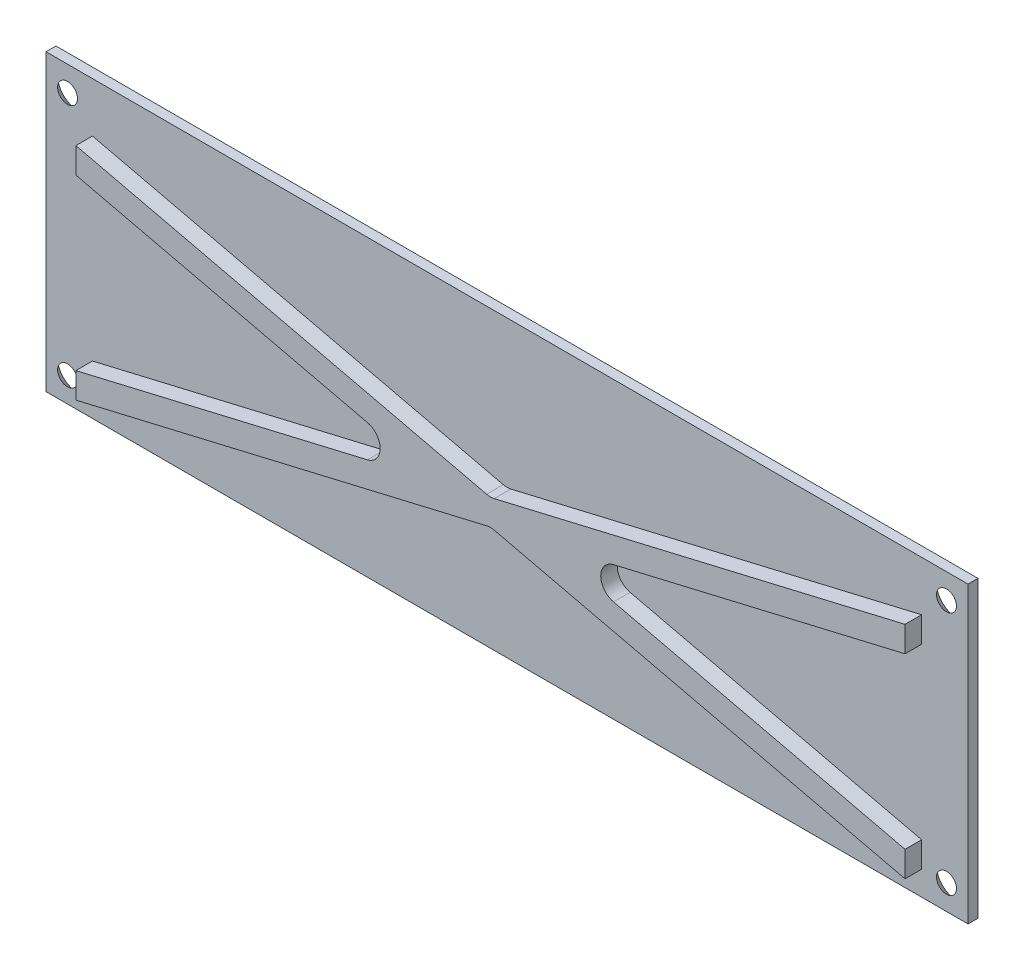
SolidWorks part; units mm, degrees
ref_plane "Front Plane" through (0, 0, 0) normal (0, 0, 1) x (1, 0, 0)
ref_plane "Top Plane" through (0, 0, 0) normal (0, 1, 0) x (1, 0, 0)
ref_plane "Right Plane" through (0, 0, 0) normal (1, 0, 0) x (0, 0, -1)
sketch "Sketch1" plane through (0, 0, 0) normal (0, 0, 1) x (1, 0, 0)
  line L1 (-56, -17.75) -> (56, -17.75)
  line L2 (-56, -17.75) -> (-56, 17.75)
  line L3 (-56, 17.75) -> (56, 17.75)
  line L4 (56, -17.75) -> (56, 17.75)
  line L5 (-56, -17.75) -> (56, 17.75) construction
  line L6 (-56, 17.75) -> (56, -17.75) construction
  point P0 (0, 0)
  dimension "D1" = 112
  dimension "D2" = 35.5
extrude "Boss-Extrude1" add sketch "Sketch1" along normal blind 1.2
sketch "Sketch2" plane through (0, 0, 1.2) normal (0, 0, 1) x (1, 0, 0)
  line L0 (0, -17.75) -> (0, 17.75) construction
  line L1 (-56, 17.75) -> (-50, 17.75)
  line L2 (-56, 17.75) -> (-56, 11.75)
  line L3 (-56, 11.75) -> (-50, 11.75)
  line L4 (-50, 17.75) -> (-50, 11.75)
  line L5 (-56, -17.75) -> (56, -17.75) construction
  line L6 (56, 17.75) -> (-56, 17.75) construction
  line L7 (-56, 0) -> (56, 0) construction
  line L8 (-56, 17.75) -> (-56, -17.75) construction
  line L9 (56, -17.75) -> (56, 17.75) construction
  line L10 (-50, -17.75) -> (-50, -11.75)
  line L11 (-56, -11.75) -> (-50, -11.75)
  line L12 (-56, -17.75) -> (-56, -11.75)
  line L13 (-56, -17.75) -> (-50, -17.75)
  line L14 (56, -17.75) -> (50, -17.75)
  line L15 (56, -17.75) -> (56, -11.75)
  line L16 (56, -11.75) -> (50, -11.75)
  line L17 (50, -17.75) -> (50, -11.75)
  line L18 (50, 17.75) -> (50, 11.75)
  line L19 (56, 11.75) -> (50, 11.75)
  line L20 (56, 17.75) -> (56, 11.75)
  line L21 (56, 17.75) -> (50, 17.75)
  dimension "D1" = 6
extrude "Boss-Extrude2" add sketch "Sketch2" along normal blind 2
sketch "Sketch3" plane through (0, 0, 3.2) normal (0, 0, 1) x (1, 0, 0)
  line L0 (-56, 0) -> (56, 0) construction
  line L1 (-56, 11.75) -> (-56, -11.75) construction
  line L2 (56, -11.75) -> (56, 11.75) construction
  line L3 (0, 17.75) -> (0, -17.75) construction
  line L4 (50, 17.75) -> (-50, 17.75) construction
  line L5 (-50, -17.75) -> (50, -17.75) construction
  line L6 (-56, 11.75) -> (-50, 17.75) construction
  line L7 (-56, -11.75) -> (-50, -17.75) construction
  line L8 (56, -11.75) -> (50, -17.75) construction
  line L9 (56, 11.75) -> (50, 17.75) construction
  circle A0 centre (-53, 14.75) radius 1.1
  circle A1 centre (-53, -14.75) radius 1.1
  circle A2 centre (53, -14.75) radius 1.1
  circle A3 centre (53, 14.75) radius 1.1
  dimension "D1" = 2.2
extrude "Cut-Extrude1" cut sketch "Sketch3" against normal through all
sketch "Sketch7" plane through (0, 0, 0) normal (0, 0, -1) x (-1, 0, 0)
  line L0 (56, -17.75) -> (-56, -17.75) construction
  line L1 (-56, 17.75) -> (-55.6, 17.75)
  line L2 (-56, 17.75) -> (-56, -17.75)
  line L3 (-56, -17.75) -> (-55.6, -17.75)
  line L4 (-55.6, 17.75) -> (-55.6, -17.75)
  line L6 (56, 17.75) -> (55.6, 17.75)
  line L7 (56, 17.75) -> (56, -17.75)
  line L8 (56, -17.75) -> (55.6, -17.75)
  line L9 (55.6, 17.75) -> (55.6, -17.75)
  dimension "D1" = 0.4
extrude "Cut-Extrude5" cut sketch "Sketch7" against normal through all
sketch "Skizze5" plane through (0, 0, 1.2) normal (0, 0, 1) x (1, 0, 0)
  line L0 (-50, 11.75) -> (0, 0)
  line L1 (50, 11.75) -> (0, 0)
  line L2 (-55.6, 9.9843) -> (-6.5569, -1.5409)
  line L3 (-50, -11.75) -> (-50, -14.8317)
  line L4 (50, -14.8317) -> (50, -11.75)
  line L5 (-55.6, 11.75) -> (-55.6, -11.75) construction
  line L7 (-50, -14.8317) -> (0, -3.0817)
  line L8 (55.6, -11.75) -> (55.6, 11.75) construction
  line L9 (-55.6, 9.9843) -> (-55.6, 11.75)
  line L10 (-55.6, 11.75) -> (-50, 11.75)
  line L11 (50, 11.75) -> (55.6, 11.75)
  line L12 (55.6, 11.75) -> (55.6, 9.9843)
  line L13 (6.5569, -1.5409) -> (50, -11.75)
  line L14 (0, -3.0817) -> (50, -14.8317)
  line L15 (-6.5569, -1.5409) -> (-50, -11.75)
  line L16 (6.5569, -1.5409) -> (55.6, 9.9843)
  dimension "D1" = 3
  dimension "D2" = 3
extrude "Aufsatz-Linear austragen2" add sketch "Skizze5" along normal up to surface (2 mm away) up to face at (-52.8, 14.75, 3.2)
fillet "Verrundung1" radius 2 4 edges at (0, -3.0817, 2.2) (0, 0, 2.2) (-6.5569, -1.5409, 2.2) (6.5569, -1.5409, 2.2)
sketch "Sketch8" plane through (0, 0, 1.2) normal (0, 0, 1) x (1, 0, 0)
  line L1 (-50, 17.75) -> (-55.6, 17.75)
  line L2 (-50, 17.75) -> (-50, -17.75)
  line L3 (-50, -17.75) -> (-55.6, -17.75)
  line L4 (-55.6, 17.75) -> (-55.6, -17.75)
  line L5 (50, 17.75) -> (55.6, 17.75)
  line L6 (50, 17.75) -> (50, -17.75)
  line L7 (50, -17.75) -> (55.6, -17.75)
  line L8 (55.6, 17.75) -> (55.6, -17.75)
extrude "Cut-Extrude7" cut sketch "Sketch8" along normal up to surface (2 mm away) up to face at (0, -1.7508, 3.2)
chamfer "Chamfer1" distance 1.3 angle 45 4 edges at (51.9, 14.75, 0) (-54.1, -14.75, 0) (-51.9, 14.75, 0) (54.1, -14.75, 0)
